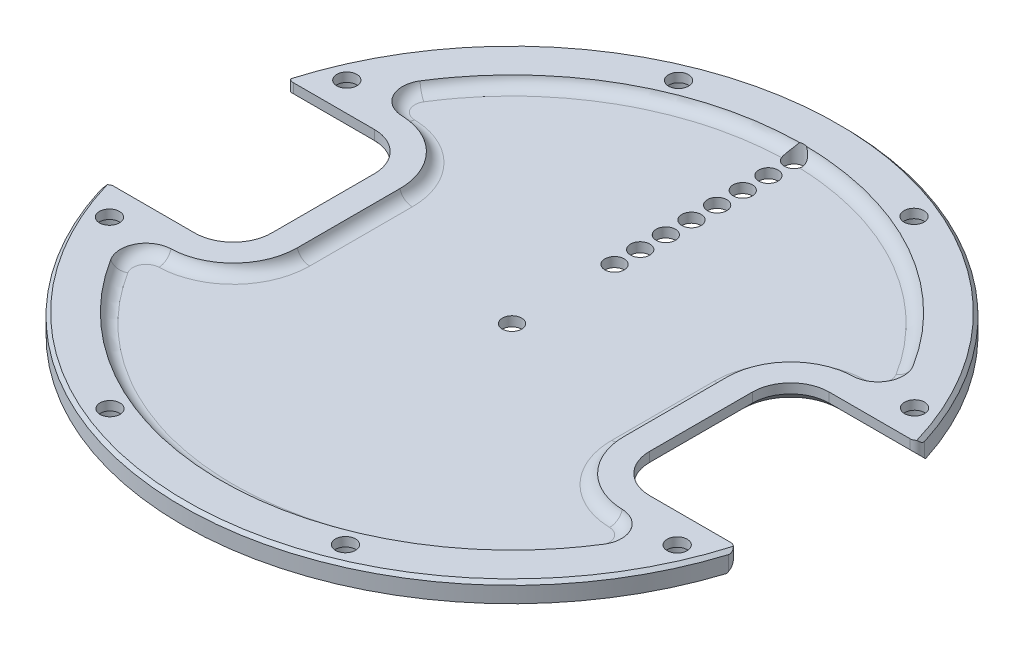
SolidWorks part; units mm, degrees
material "6061 Alloy"
ref_plane "Front Plane" through (0, 0, 0) normal (0, 0, 1) x (1, 0, 0)
ref_plane "Top Plane" through (0, 0, 0) normal (0, 1, 0) x (1, 0, 0)
ref_plane "Right Plane" through (0, 0, 0) normal (1, 0, 0) x (0, 0, -1)
sketch "Sketch1" plane through (0, 0, 0) normal (0, 1, 0) x (1, 0, 0)
  circle A0 centre (0, 0) radius 81.6102
  dimension "D1" = 163.2204
extrude "Boss-Extrude1" add sketch "Sketch1" along normal blind 4.7625
sketch "Sketch2" plane through (0, 0, 0) normal (0, 1, 0) x (1, 0, 0)
  line L0 (-46.8122, 0) -> (0, 0) construction
  line L1 (-81.6102, 22.225) -> (-56.3372, 22.225)
  line L2 (-81.6102, 22.225) -> (-81.6102, -22.225)
  line L3 (-81.6102, -22.225) -> (-56.3372, -22.225)
  line L4 (-46.8122, 12.7) -> (-46.8122, -12.7)
  line L5 (81.6102, 22.225) -> (56.3372, 22.225)
  line L6 (81.6102, 22.225) -> (81.6102, -22.225)
  line L7 (81.6102, -22.225) -> (56.3372, -22.225)
  line L8 (46.8122, 12.7) -> (46.8122, -12.7)
  line L9 (0, 0) -> (46.8122, 0) construction
  arc A0 (56.3372, 22.225) -> (46.8122, 12.7) centre (56.3372, 12.7) ccw
  arc A1 (46.8122, -12.7) -> (56.3372, -22.225) centre (56.3372, -12.7) ccw
  arc A2 (-56.3372, -22.225) -> (-46.8122, -12.7) centre (-56.3372, -12.7) ccw
  arc A3 (-46.8122, 12.7) -> (-56.3372, 22.225) centre (-56.3372, 12.7) ccw
  circle A4 centre (0, 0) radius 81.6102 construction
  dimension "D1" = 9.525
  dimension "D2" = 46.8122
  dimension "D3" = 44.45
extrude "Cut-Extrude1" cut sketch "Sketch2" along normal through all both and the other way through all
sketch "Sketch3" plane through (0, 4.7625, 0) normal (0, 1, 0) x (1, 0, 0)
  line L1 (-40.4622, 12.7) -> (-40.4622, -12.7)
  line L4 (40.4622, -12.7) -> (40.4622, 12.7)
  line L6 (-46.8122, -12.7) -> (-46.8122, 12.7) construction
  line L7 (0, 81.6102) -> (0, 72.0852) construction
  arc A0 (-61.0759, -38.2886) -> (61.0759, -38.2886) centre (0, 0) ccw
  arc A1 (61.0759, 38.2886) -> (-61.0759, 38.2886) centre (0, 0) ccw
  arc A2 (-61.0759, -38.2886) -> (-55.879, -28.5684) centre (-55.6957, -34.9157) cw
  arc A3 (55.879, -28.5684) -> (61.0759, -38.2886) centre (55.6957, -34.9157) cw
  arc A4 (61.0759, 38.2886) -> (55.879, 28.5684) centre (55.6957, 34.9157) cw
  arc A5 (-61.0759, 38.2886) -> (-55.879, 28.5684) centre (-55.6957, 34.9157) ccw
  arc A6 (40.4622, 12.7) -> (55.879, 28.5684) centre (56.3372, 12.7) cw
  arc A7 (40.4622, -12.7) -> (55.879, -28.5684) centre (56.3372, -12.7) ccw
  arc A8 (-55.879, -28.5684) -> (-40.4622, -12.7) centre (-56.3372, -12.7) ccw
  arc A9 (-55.879, 28.5684) -> (-40.4622, 12.7) centre (-56.3372, 12.7) cw
  arc A10 (-46.8122, 12.7) -> (-56.3372, 22.225) centre (-56.3372, 12.7) ccw construction
  arc A11 (-56.3372, -22.225) -> (-46.8122, -12.7) centre (-56.3372, -12.7) ccw construction
  arc A12 (56.3372, 22.225) -> (46.8122, 12.7) centre (56.3372, 12.7) ccw construction
  arc A13 (78.5256, 22.225) -> (-78.5256, 22.225) centre (0, 0) ccw construction
  dimension "D1" = 6.35
  dimension "D2" = 6.35
  dimension "D3" = 9.525
extrude "Cut-Extrude2" cut sketch "Sketch3" against normal offset from surface 2.3876 and the other way through all up to face at (0, 0, 0)
chamfer "Chamfer1" distance 2.3876 angle 45 10 edges
fillet "Fillet2" radius 3.175 12 edges at (-44.951, 2.3876, 23.7621) (-40.4622, 2.3876, 0) (-44.951, 2.3876, -23.7621) (-61.2956, 2.3876, -31.9218) (0, 2.3876, -72.0852) (61.2956, 2.3876, -31.9218) (44.951, 2.3876, -23.7621) (40.4622, 2.3876, 0) (44.951, 2.3876, 23.7621) (61.2956, 2.3876, 31.9218) (0, 2.3876, 72.0852) (-61.2956, 2.3876, 31.9218)
sketch "Sketch8" plane through (0, 2.3876, 0) normal (0, 1, 0) x (1, 0, 0)
  line L0 (-3.81, 73.1774) -> (-3.81, 22.0726) construction
  line L1 (-3.81, 22.0726) -> (6.4008, 22.0726) construction
  line L2 (6.4008, 22.0726) -> (6.4008, 73.1774) construction
  line L3 (6.4008, 73.1774) -> (-3.81, 73.1774) construction
  line L4 (4.1148, 60.325) -> (4.1148, 34.925) construction
  line L5 (0, 69.85) -> (0, 73.1774) construction
  line L6 (4.1148, 60.325) -> (4.1148, 73.1774) construction
  line L7 (4.1148, 34.925) -> (4.1148, 22.0726) construction
  line L8 (0, 69.85) -> (0, 63.5) construction
  line L9 (0, 63.5) -> (0, 57.15) construction
  line L10 (0, 57.15) -> (0, 50.8) construction
  line L11 (0, 50.8) -> (0, 44.45) construction
  line L12 (0, 44.45) -> (0, 38.1) construction
  line L13 (0, 38.1) -> (0, 31.75) construction
  line L14 (0, 31.75) -> (0, 25.4) construction
  line L15 (0, 25.4) -> (0, 22.0726) construction
  circle A0 centre (4.1148, 60.325) radius 0.889 construction
  circle A1 centre (4.1148, 34.925) radius 0.889 construction
  circle A2 centre (0, 69.85) radius 2.3876
  circle A3 centre (0, 63.5) radius 2.3876
  circle A4 centre (0, 57.15) radius 2.3876
  circle A5 centre (0, 50.8) radius 2.3876
  circle A6 centre (0, 44.45) radius 2.3876
  circle A7 centre (0, 38.1) radius 2.3876
  circle A8 centre (0, 31.75) radius 2.3876
  circle A9 centre (0, 25.4) radius 2.3876
  circle A10 centre (0, 0) radius 2.3876
  dimension "D5" = 1.778
  dimension "D7" = 4.7752
  dimension "D1" = 51.1048
  dimension "D2" = 10.2108
  dimension "D3" = 25.4
  dimension "D4" = 7.9248
  dimension "D6" = 6.35
  dimension "D8" = 3.81
  dimension "D9" = 25.4
extrude "Cut-Extrude5" cut sketch "Sketch8" against normal through all both and the other way through all
chamfer "Chamfer3" distance 0.8128 angle 45 2 edges at (0, 4.7625, -81.6102) (0, 4.7625, 81.6102)
fillet "Fillet4" radius 1.6002 4 edges at (78.5256, 3.1687, -22.225) (78.5256, 3.1687, 22.225) (-78.5256, 3.1687, 22.225) (-78.5256, 3.1687, -22.225)
sketch "Sketch10" plane through (0, 0, 0) normal (0, -1, 0) x (1, 0, 0)
  line L0 (-70.3025, 29.3938) -> (0, 0) construction
  line L1 (2.6469, 0) -> (-2.6469, 0) construction
  line L2 (-29.1605, 70.3996) -> (0, 0) construction
  line L3 (0, -2.6469) -> (0, 2.6469) construction
  circle A0 centre (-70.3025, 29.3938) radius 4.0259
  circle A1 centre (-29.1605, 70.3996) radius 4.0259
  dimension "D4" = 8.0518
  dimension "D1" = 22.69
  dimension "D2" = 76.2
  dimension "D3" = 22.5
extrude "Cut-Extrude6" cut sketch "Sketch10" against normal blind 2.5095 and the other way through all
sketch "Sketch11" plane through (0, 2.5095, 0) normal (0, -1, 0) x (1, 0, 0)
  circle A0 centre (-70.3025, 29.3938) radius 2.4765
  circle A1 centre (-29.1605, 70.3996) radius 2.4765
  dimension "D1" = 4.953
extrude "Cut-Extrude7" cut sketch "Sketch11" against normal through all both and the other way through all
mirror "Mirror1" about plane through (0, 0, 0) normal (1, 0, 0) of "Cut-Extrude7", "Cut-Extrude6"
mirror "Mirror2" about plane through (0, 0, 0) normal (0, 0, 1) of "Cut-Extrude7", "Cut-Extrude6", "Mirror1"
